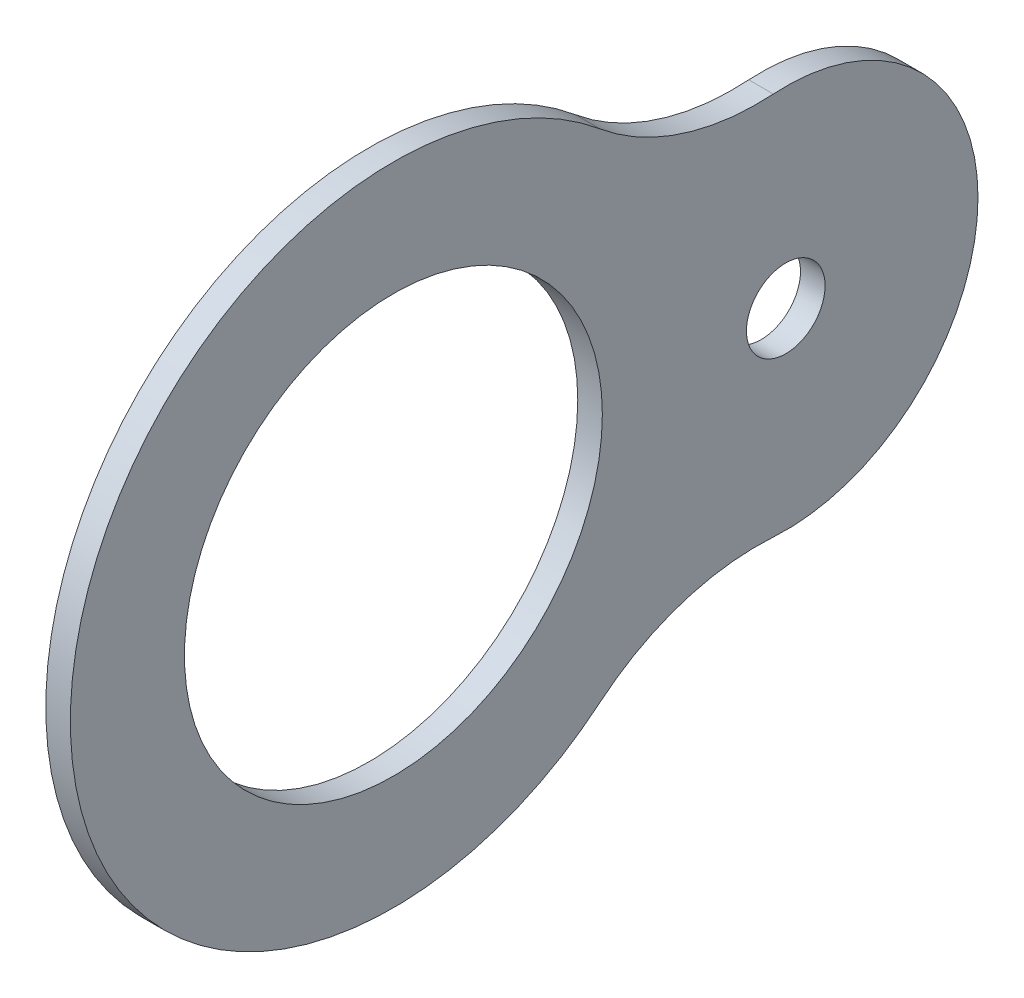
SolidWorks part; units mm, degrees
material "ABS"
ref_plane "Спереди" through (0, 0, 0) normal (0, 0, 1) x (1, 0, 0)
ref_plane "Сверху" through (0, 0, 0) normal (0, 1, 0) x (1, 0, 0)
ref_plane "Справа" through (0, 0, 0) normal (1, 0, 0) x (0, 0, -1)
sketch "Эскиз1" plane through (0, 0, 0) normal (1, 0, 0) x (0, 0, -1)
  circle A0 centre (27.5751, 7.5072) radius 1.5
  circle A1 centre (27.5751, 7.5072) radius 18.465
  circle A2 centre (14.9975, 25.9822) radius 7.885
  circle A3 centre (14.9975, 25.9822) radius 1.5
  circle A4 centre (0, 0) radius 13.14
  circle A5 centre (15.96, 0) radius 7.82
  circle A6 centre (0, 0) radius 8.5
  circle A7 centre (15.96, 0) radius 1.6
  point P6 (15.96, 0)
  point P7 (0, 0)
  dimension "D1" = 3
  dimension "D2" = 36.93
  dimension "D3" = 15.77
  dimension "D5" = 3
  dimension "D10" = 26.28
  dimension "D11" = 15.64
  dimension "D12" = 17
  dimension "D13" = 3.2
  dimension "D4" = 22.35
  dimension "D6" = 15.96
  dimension "D7" = 30
  dimension "D8" = 26
  dimension "D9" = 13.83
extrude "Бобышка-Вытянуть1" add sketch "Эскиз1" along normal blind 1 contours A5 A1 A4 | A1 A5 A4 | A4 A5 A1 | A5 A4 A1 | A1 A5 A4 A7 | A4 A5 A1 region at (0, -6.2019, -13.7944) region at (0, 0.4874, -17.9076) region at (0, -1.7689, -10.1647) region at (0, 1.9218, -11.5291) region at (0, -1.8181, 12.6499) region at (0, 6.8202, -9.9491)
fillet "Скругление1" radius 10 2 edges at (0.5, -6.4049, -11.4733) (0.5, 6.4049, -11.4733)
